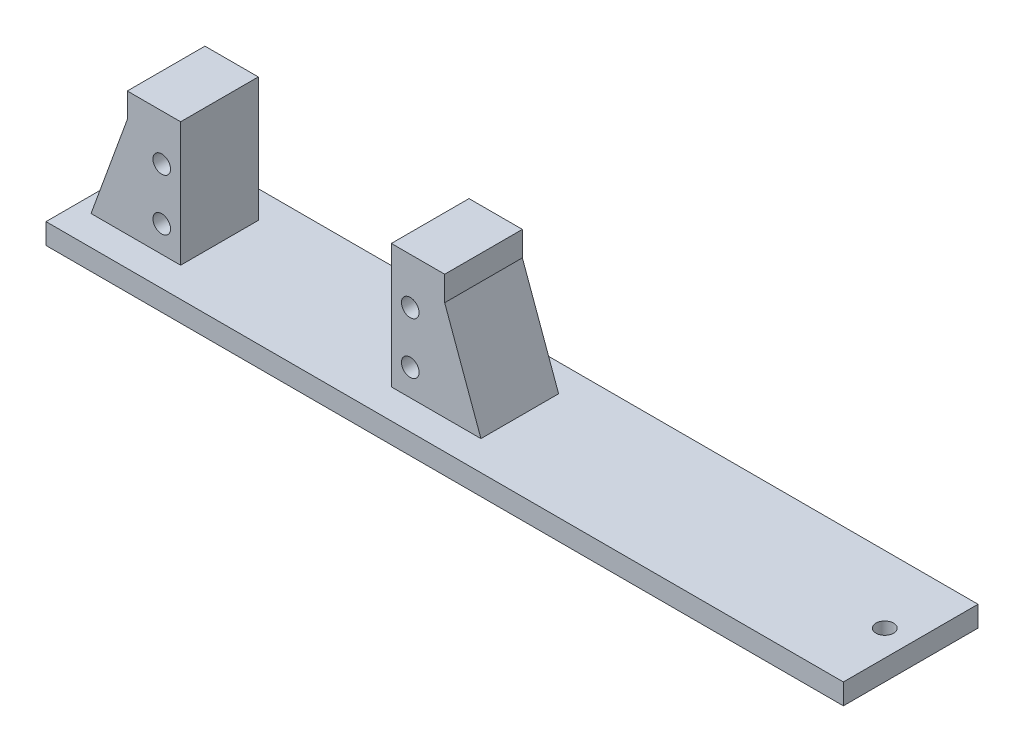
SolidWorks part; units mm, degrees
ref_plane "Front Plane" through (0, 0, 0) normal (0, 0, 1) x (1, 0, 0)
ref_plane "Top Plane" through (0, 0, 0) normal (0, 1, 0) x (1, 0, 0)
ref_plane "Right Plane" through (0, 0, 0) normal (1, 0, 0) x (0, 0, -1)
other "Configuration Table"
sketch "Sketch1" plane through (0, 0, 0) normal (0, 1, 0) x (1, 0, 0)
  line L0 (-77, 79) -> (-77, 53)
  line L1 (-72, 66) -> (72, 66) construction
  line L2 (-72, 66) -> (-72, 0) construction
  line L3 (-72, -66) -> (-70.3, -66) construction
  line L4 (72, 66) -> (72, 0) construction
  line L5 (-72, 66) -> (0, 0) construction
  line L6 (-72, -66) -> (-70.7468, -64.8513) construction
  line L7 (-77, -89) -> (77, -89) construction
  line L8 (77, 79) -> (77, 53)
  line L9 (-77, 89) -> (77, 89) construction
  line L10 (-77, 0) -> (-72, 0) construction
  line L11 (-77, 0) -> (-77, -89) construction
  line L12 (-72, 0) -> (-72, -64.3) construction
  line L13 (-72, -64.3) -> (-72, -66) construction
  line L14 (70.3, -66) -> (72, -66) construction
  line L15 (0, 0) -> (70.7468, -64.8513) construction
  line L16 (70.7468, -64.8513) -> (72, -66) construction
  line L17 (72, 0) -> (72, -64.3) construction
  line L18 (72, -64.3) -> (72, -66) construction
  line L19 (77, 0) -> (77, -89) construction
  line L20 (-70.3, -66) -> (70.3, -66) construction
  line L21 (-70.7468, -64.8513) -> (0, 0) construction
  line L22 (0, 0) -> (72, 66) construction
  line L23 (-77, 53) -> (77, 53)
  line L24 (-77, 53) -> (-77, 0) construction
  line L25 (-72, 0) -> (0, 0) construction
  line L26 (72, 0) -> (77, 0) construction
  line L27 (0, 0) -> (72, 0) construction
  line L28 (77, 53) -> (77, 0) construction
  line L29 (-77, 79) -> (77, 79)
  line L30 (-77, 89) -> (-77, 79) construction
  line L31 (77, 89) -> (77, 79) construction
  arc A0 (-70.3, -66) -> (-70.7468, -64.8513) centre (-72, -66) ccw construction
  arc A1 (72, -64.3) -> (70.7468, -64.8513) centre (72, -66) ccw construction
  circle A2 centre (72, 66) radius 1.7
  circle A3 centre (-72, 66) radius 1.7
  arc A4 (-72, -64.3) -> (-70.3, -66) centre (-72, -66) ccw construction
  arc A5 (70.3, -66) -> (72, -64.3) centre (72, -66) ccw construction
  arc A6 (70.7468, -64.8513) -> (70.3, -66) centre (72, -66) ccw construction
  arc A7 (-70.7468, -64.8513) -> (-72, -64.3) centre (-72, -66) ccw construction
  point P0 (0, 0)
  dimension "D3" = 3.4
  dimension "D4" = 89
  dimension "D9" = 13
  dimension "D1" = 144
  dimension "D2" = 132
  dimension "D5" = 5
  dimension "D6" = 5
  dimension "D7" = 178
  dimension "D8" = 0
  dimension "D10" = 13
extrude "Boss-Extrude1" add sketch "Sketch1" along normal blind 4
sketch "Sketch3" plane through (0, 4, 0) normal (0, 1, 0) x (1, 0, 0)
  line L1 (-67, 89) -> (-5.7, 89) construction
  line L2 (-67, 73.7) -> (-67, 58.7)
  line L3 (-67, 58.7) -> (-56.7, 58.7)
  line L4 (-5.7, 73.7) -> (-5.7, 58.7)
  line L5 (-77, 79) -> (-77, 53) construction
  line L6 (-67, 73.7) -> (-56.7, 73.7)
  line L7 (-67, 89) -> (-67, 73.7) construction
  line L8 (-5.7, 89) -> (-5.7, 73.7) construction
  line L9 (-56.7, 73.7) -> (-56.7, 58.7)
  line L10 (-16, 73.7) -> (-16, 58.7)
  line L11 (-56.7, 58.7) -> (-16, 58.7) construction
  line L12 (-16, 58.7) -> (-5.7, 58.7)
  line L13 (-56.7, 73.7) -> (-16, 73.7) construction
  line L14 (-16, 73.7) -> (-5.7, 73.7)
  line L16 (-77, 89) -> (77, 89) construction
  dimension "D1" = 10
  dimension "D2" = 30.3
  dimension "D3" = 61.3
  dimension "D4" = 15
  dimension "D5" = 40.7
  dimension "D6" = 10.3
extrude "Boss-Extrude2" add sketch "Sketch3" along normal blind 24
chamfer "Chamfer2" distance 7 angle 70 1 edges at (-5.7, 4, -66.2) first distance on face at (-61.85, 4, -66.2)
chamfer "Chamfer3" distance 7 angle 70 1 edges at (-67, 4, -66.2) first distance on face at (-61.85, 4, -66.2)
sketch "Sketch4" plane through (0, 28, 0) normal (0, 1, 0) x (1, 0, 0)
  line L0 (-67, 73.7) -> (-67, 58.7) construction
  line L1 (-77, 71) -> (-67, 71)
  line L2 (-77, 71) -> (-77, 61)
  line L3 (-77, 61) -> (-67, 61)
  line L4 (-67, 71) -> (-67, 61)
  line L5 (-77, 71) -> (-67, 61) construction
  line L6 (-77, 61) -> (-67, 71) construction
  point P0 (-72, 66)
extrude "Cut-Extrude1" cut sketch "Sketch4" against normal up to surface (24 mm away) up to face at (-65.35, 4, -66.2)
sketch "Sketch6" plane through (0, 0, -58.7) normal (0, 0, 1) x (1, 0, 0)
  line L0 (-16, 4) -> (1.3, 4) construction
  line L1 (1.3, 4) -> (-5.7, 23.2323) construction
  line L2 (-5.7, 23.2323) -> (-5.7, 28) construction
  line L3 (-5.7, 28) -> (-16, 28) construction
  line L4 (-16, 28) -> (-16, 4) construction
  line L5 (-67, 28) -> (-67, 23.2323) construction
  line L7 (-56.7, 4) -> (-56.7, 28) construction
  line L8 (-56.7, 28) -> (-67, 28) construction
  line L9 (-16, 4) -> (1.3, 4) construction
  line L10 (1.3, 4) -> (-5.7, 23.2323) construction
  line L11 (-5.7, 23.2323) -> (-5.7, 28) construction
  line L12 (-5.7, 28) -> (-16, 28) construction
  line L13 (-16, 28) -> (-16, 4) construction
  line L14 (-67, 28) -> (-67, 23.2323) construction
  line L16 (-56.7, 4) -> (-56.7, 28) construction
  line L17 (-56.7, 28) -> (-67, 28) construction
  line L18 (-60.35, 28) -> (-60.35, 4) construction
  line L19 (-12.35, 28) -> (-12.35, 4) construction
  line L20 (-67, 23.2323) -> (-67, 4) construction
  line L21 (-74, 4) -> (-56.7, 4) construction
  line L22 (-67, 4) -> (-56.7, 4) construction
  circle A0 centre (-60.35, 9.1) radius 1.7
  circle A1 centre (-60.35, 19.1) radius 1.7
  circle A2 centre (-12.35, 9.1) radius 1.7
  circle A3 centre (-12.35, 19.1) radius 1.7
  dimension "D1" = 10
  dimension "D2" = 3.4
  dimension "D4" = 3.65
  dimension "D5" = 3.65
  dimension "D3" = 5.1
  dimension "D6" = 21.8168
extrude "Cut-Extrude2" cut sketch "Sketch6" against normal up to surface (15 mm away) up to face at (-64.28, 17.4465, -73.7)
sketch "Sketch7" [suppressed] plane through (0, 4, 0) normal (0, 1, 0) x (1, 0, 0)
  line L0 (-77, 53) -> (77, 53) construction
  line L1 (-64.5, 53) -> (-28.5, 53)
  line L2 (-64.5, 53) -> (-64.5, 61)
  line L3 (-64.5, 61) -> (-28.5, 61)
  line L4 (-28.5, 53) -> (-28.5, 61)
  line L6 (-46.5, 61) -> (-46.5, 53) construction
  line L7 (-77, 82) -> (-77, 53) construction
  dimension "D1" = 36
  dimension "D2" = 8
  dimension "D3" = 30.5
extrude "Boss-Extrude3" [suppressed] add sketch "Sketch7" along normal blind 29
sketch "Sketch8" [suppressed] plane through (0, 0, -53) normal (0, 0, 1) x (1, 0, 0)
  line L0 (-28.5, 4) -> (-64.5, 4) construction
  line L1 (-28.5, 4) -> (-64.5, 4) construction
  line L2 (-77, 4) -> (-77, 0) construction
  circle A0 centre (-46.5, 14.1) radius 11.1
  dimension "D1" = 22.2
  dimension "D2" = 10.1
  dimension "D3" = 30.5
extrude "Cut-Extrude3" [suppressed] cut sketch "Sketch8" against normal up to surface (8 mm away)
sketch "Sketch9" [suppressed] plane through (0, 0, -61) normal (0, 0, -1) x (-1, 0, 0)
  line L0 (41.8957, 4) -> (51.1043, 4)
  line L4 (28.5, 4) -> (41.8957, 4)
  line L5 (64.5, 4) -> (64.5, 33)
  line L6 (64.5, 33) -> (28.5, 33)
  line L7 (28.5, 33) -> (28.5, 4)
  line L8 (28.5, 4) -> (41.8957, 4)
  line L9 (64.5, 4) -> (64.5, 33)
  line L10 (64.5, 33) -> (28.5, 33)
  line L11 (28.5, 33) -> (28.5, 4)
  line L13 (51.1043, 4) -> (64.5, 4)
  line L14 (51.1043, 4) -> (64.5, 4)
  circle A0 centre (46.5, 14.1) radius 6
  arc A2 (51.1043, 4) -> (41.8957, 4) centre (46.5, 14.1) ccw
  arc A3 (51.1043, 4) -> (41.8957, 4) centre (46.5, 14.1) ccw construction
  dimension "D2" = 12
  dimension "D1" = 0
extrude "Boss-Extrude4" [suppressed] add sketch "Sketch9" along normal blind 3
chamfer "Chamfer4" [suppressed] distance 7 angle 70
fillet "Fillet1" [suppressed] radius 6
fillet "Fillet2" [suppressed] radius 1
equation "\"D3@Sketch3\"=56.3+5"
equation "\"D2@Sketch3\"=27.70mm+2.6mm"
